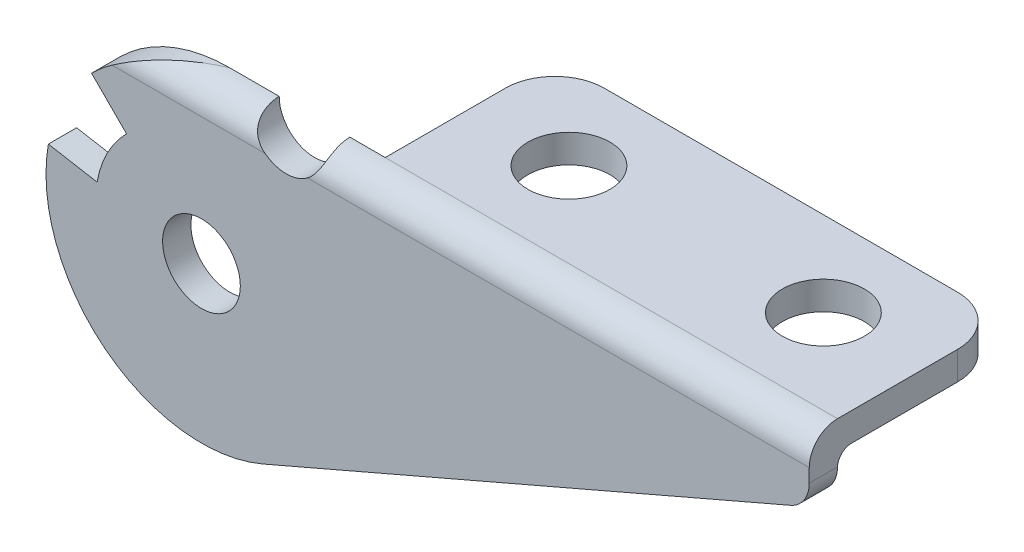
SolidWorks part; units mm, degrees
ref_plane "Front" through (0, 0, 0) normal (0, 0, 1) x (1, 0, 0)
ref_plane "Top" through (0, 0, 0) normal (0, 1, 0) x (1, 0, 0)
ref_plane "Right" through (0, 0, 0) normal (1, 0, 0) x (0, 0, -1)
ref_plane "Plane1" through (0, 0, 0) normal (0, 0, 1) x (1, 0, 0)
sketch "Sketch1" plane through (0, 0, 0) normal (0, 0, 1) x (1, 0, 0)
  line L0 (4.3638, 0.9026) -> (41.6728, 17.0264)
  line L1 (43, 19.0459) -> (43, 22)
  line L2 (43, 22) -> (0, 22)
  line L3 (-7.7782, 18.7782) -> (-5.3033, 16.3033)
  line L4 (-7.3861, 12.3024) -> (-10.8329, 12.9101)
  arc A0 (-10.8329, 12.9101) -> (4.3638, 0.9026) centre (0, 11) ccw
  arc A1 (41.6728, 17.0264) -> (43, 19.0459) centre (40.8, 19.0459) ccw
  arc A2 (0, 22) -> (-7.7782, 18.7782) centre (0, 11) ccw
  arc A3 (-5.3033, 16.3033) -> (-7.3861, 12.3024) centre (0, 11) ccw
  circle A4 centre (0, 11) radius 2.75
extrude "Boss-Extrude1" add sketch "Sketch1" against normal blind 14
ref_plane "Plane2" through (0, 0, 0) normal (1, 0, 0) x (0, 0, -1)
sketch "Sketch2" plane through (0, 0, 0) normal (1, 0, 0) x (0, 0, -1)
  line L0 (-5, -5) -> (19, -5)
  line L1 (19, -5) -> (19, 27)
  line L2 (19, 27) -> (-5, 27)
  line L3 (-5, 27) -> (-5, -5)
  line L4 (0, 0) -> (2, 0)
  line L5 (2, 0) -> (2, 19)
  line L6 (3, 20) -> (14, 20)
  line L7 (14, 20) -> (14, 22)
  line L8 (14, 22) -> (2, 22)
  line L9 (0, 20) -> (0, 0)
  arc A0 (2, 19) -> (3, 20) centre (3, 19) cw
  arc A1 (2, 22) -> (0, 20) centre (2, 20) ccw
extrude "Cut-Extrude1" cut sketch "Sketch2" against normal blind 65 and the other way blind 65
ref_plane "Plane3" through (0, 0, 0) normal (0, 1, 0) x (-1, 0, 0)
sketch "Sketch3" plane through (0, 0, 0) normal (0, 1, 0) x (-1, 0, 0)
  line L0 (16, 5) -> (-48, 5)
  line L1 (-48, 5) -> (-48, -19)
  line L2 (-48, -19) -> (16, -19)
  line L3 (16, -19) -> (16, 5)
  line L4 (11, 0) -> (-43, 0)
  line L5 (-43, 0) -> (-43, -10.5)
  line L6 (-39.5, -14) -> (-14.5, -14)
  line L7 (-11, -10.5) -> (-11, -2)
  line L8 (-11, -2) -> (11, -2)
  line L9 (11, -2) -> (11, 0)
  arc A0 (-43, -10.5) -> (-39.5, -14) centre (-39.5, -10.5) ccw
  arc A1 (-14.5, -14) -> (-11, -10.5) centre (-14.5, -10.5) ccw
extrude "Cut-Extrude2" cut sketch "Sketch3" along normal blind 22
ref_plane "Plane4" through (0, 22, 0) normal (0, 1, 0) x (-1, 0, 0)
sketch "Sketch4" plane through (0, 22, 0) normal (0, 1, 0) x (-1, 0, 0)
  circle A0 centre (-18, -8) radius 2.9
extrude "Cut-Extrude3" cut sketch "Sketch4" against normal blind 2 and the other way blind 2
ref_plane "Plane5" through (0, 22, 0) normal (0, 1, 0) x (-1, 0, 0)
sketch "Sketch5" plane through (0, 22, 0) normal (0, 1, 0) x (-1, 0, 0)
  circle A0 centre (-36, -8) radius 2.9
extrude "Cut-Extrude4" cut sketch "Sketch5" against normal blind 2 and the other way blind 2
ref_plane "Plane6" through (0, 0, 0) normal (0, 0, 1) x (1, 0, 0)
sketch "Sketch6" plane through (0, 0, 0) normal (0, 0, 1) x (1, 0, 0)
  circle A0 centre (6, 22) radius 2.5
extrude "Cut-Extrude5" cut sketch "Sketch6" against normal blind 14
